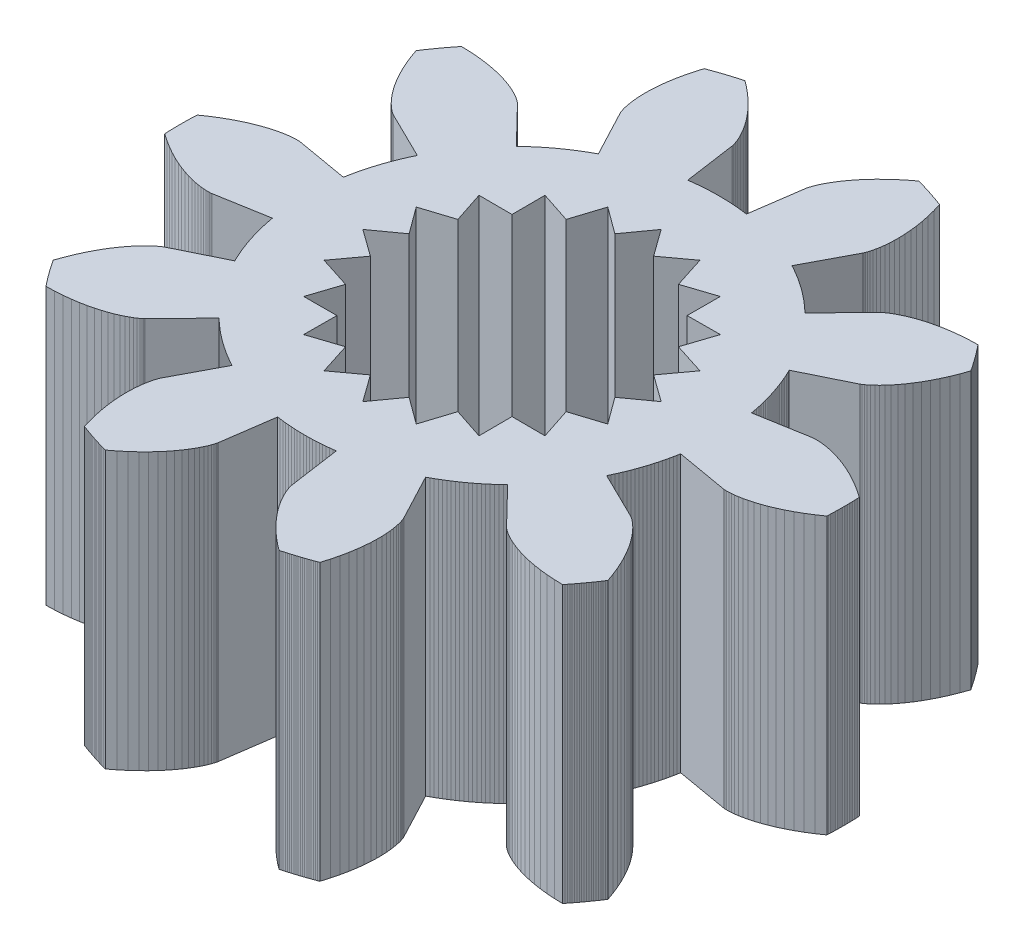
SolidWorks part; units mm, degrees
ref_plane "Front Plane" through (0, 0, 0) normal (0, 0, 1) x (1, 0, 0)
ref_plane "Top Plane" through (0, 0, 0) normal (0, 1, 0) x (1, 0, 0)
ref_plane "Right Plane" through (0, 0, 0) normal (1, 0, 0) x (0, 0, -1)
sketch "Sketch1" plane through (0, 0, 0) normal (0, 1, 0) x (1, 0, 0)
  line L0 (3.6947, -0.6418) -> (4.6291, -0.8041)
  line L1 (4.6291, -0.8041) -> (4.6332, -0.8047)
  line L2 (4.6332, -0.8047) -> (4.6455, -0.806)
  line L3 (4.6455, -0.806) -> (4.6659, -0.8073)
  line L4 (4.6659, -0.8073) -> (4.6947, -0.8081)
  line L5 (4.6947, -0.8081) -> (4.7316, -0.8074)
  line L6 (4.7316, -0.8074) -> (4.7767, -0.8048)
  line L7 (4.7767, -0.8048) -> (4.8297, -0.7994)
  line L8 (4.8297, -0.7994) -> (4.8907, -0.7907)
  line L9 (4.8907, -0.7907) -> (4.9593, -0.778)
  line L10 (4.9593, -0.778) -> (5.0353, -0.7605)
  line L11 (5.0353, -0.7605) -> (5.1184, -0.7378)
  line L12 (5.1184, -0.7378) -> (5.2084, -0.7091)
  line L13 (5.2084, -0.7091) -> (5.3047, -0.6738)
  line L14 (5.3047, -0.6738) -> (5.4071, -0.6314)
  line L15 (5.4071, -0.6314) -> (5.5151, -0.5813)
  line L16 (5.5151, -0.5813) -> (5.6282, -0.523)
  line L17 (5.6282, -0.523) -> (5.7459, -0.456)
  line L18 (5.7459, -0.456) -> (5.8676, -0.3797)
  line L19 (5.8676, -0.3797) -> (5.9928, -0.2937)
  line L20 (5.9928, -0.2937) -> (5.9942, -0.2628)
  line L21 (5.9942, -0.2628) -> (5.9955, -0.2319)
  line L22 (5.9955, -0.2319) -> (5.9966, -0.201)
  line L23 (5.9966, -0.201) -> (5.9976, -0.1701)
  line L24 (5.9976, -0.1701) -> (5.9984, -0.1392)
  line L25 (5.9984, -0.1392) -> (5.999, -0.1083)
  line L26 (5.999, -0.1083) -> (5.9995, -0.0773)
  line L27 (5.9995, -0.0773) -> (5.9998, -0.0464)
  line L28 (5.9998, -0.0464) -> (6, -0.0155)
  line L29 (6, -0.0155) -> (6, 0.0155)
  line L30 (6, 0.0155) -> (5.9998, 0.0464)
  line L31 (5.9998, 0.0464) -> (5.9995, 0.0773)
  line L32 (5.9995, 0.0773) -> (5.999, 0.1083)
  line L33 (5.999, 0.1083) -> (5.9984, 0.1392)
  line L34 (5.9984, 0.1392) -> (5.9976, 0.1701)
  line L35 (5.9976, 0.1701) -> (5.9966, 0.201)
  line L36 (5.9966, 0.201) -> (5.9955, 0.2319)
  line L37 (5.9955, 0.2319) -> (5.9942, 0.2628)
  line L38 (5.9942, 0.2628) -> (5.9928, 0.2937)
  line L39 (5.9928, 0.2937) -> (5.8676, 0.3797)
  line L40 (5.8676, 0.3797) -> (5.7459, 0.456)
  line L41 (5.7459, 0.456) -> (5.6282, 0.523)
  line L42 (5.6282, 0.523) -> (5.5151, 0.5813)
  line L43 (5.5151, 0.5813) -> (5.4071, 0.6314)
  line L44 (5.4071, 0.6314) -> (5.3047, 0.6738)
  line L45 (5.3047, 0.6738) -> (5.2084, 0.7091)
  line L46 (5.2084, 0.7091) -> (5.1184, 0.7378)
  line L47 (5.1184, 0.7378) -> (5.0353, 0.7605)
  line L48 (5.0353, 0.7605) -> (4.9593, 0.778)
  line L49 (4.9593, 0.778) -> (4.8907, 0.7907)
  line L50 (4.8907, 0.7907) -> (4.8297, 0.7994)
  line L51 (4.8297, 0.7994) -> (4.7767, 0.8048)
  line L52 (4.7767, 0.8048) -> (4.7316, 0.8074)
  line L53 (4.7316, 0.8074) -> (4.6947, 0.8081)
  line L54 (4.6947, 0.8081) -> (4.6659, 0.8073)
  line L55 (4.6659, 0.8073) -> (4.6455, 0.806)
  line L56 (4.6455, 0.806) -> (4.6332, 0.8047)
  line L57 (4.6332, 0.8047) -> (4.6291, 0.8041)
  line L58 (4.6291, 0.8041) -> (3.6947, 0.6418)
  line L59 (3.6947, 0.6418) -> (3.6847, 0.697)
  line L60 (3.6847, 0.697) -> (3.6738, 0.752)
  line L61 (3.6738, 0.752) -> (3.6621, 0.8069)
  line L62 (3.6621, 0.8069) -> (3.6497, 0.8617)
  line L63 (3.6497, 0.8617) -> (3.6364, 0.9162)
  line L64 (3.6364, 0.9162) -> (3.6222, 0.9705)
  line L65 (3.6222, 0.9705) -> (3.6073, 1.0246)
  line L66 (3.6073, 1.0246) -> (3.5916, 1.0785)
  line L67 (3.5916, 1.0785) -> (3.575, 1.1321)
  line L68 (3.575, 1.1321) -> (3.5577, 1.1855)
  line L69 (3.5577, 1.1855) -> (3.5396, 1.2386)
  line L70 (3.5396, 1.2386) -> (3.5206, 1.2914)
  line L71 (3.5206, 1.2914) -> (3.5009, 1.344)
  line L72 (3.5009, 1.344) -> (3.4804, 1.3962)
  line L73 (3.4804, 1.3962) -> (3.4591, 1.4481)
  line L74 (3.4591, 1.4481) -> (3.4371, 1.4997)
  line L75 (3.4371, 1.4997) -> (3.4142, 1.551)
  line L76 (3.4142, 1.551) -> (3.3906, 1.6019)
  line L77 (3.3906, 1.6019) -> (3.3663, 1.6525)
  line L78 (3.3663, 1.6525) -> (4.2177, 2.0704)
  line L79 (4.2177, 2.0704) -> (4.2213, 2.0723)
  line L80 (4.2213, 2.0723) -> (4.232, 2.0785)
  line L81 (4.232, 2.0785) -> (4.2494, 2.0894)
  line L82 (4.2494, 2.0894) -> (4.273, 2.1057)
  line L83 (4.273, 2.1057) -> (4.3025, 2.1279)
  line L84 (4.3025, 2.1279) -> (4.3374, 2.1566)
  line L85 (4.3374, 2.1566) -> (4.3773, 2.1921)
  line L86 (4.3773, 2.1921) -> (4.4214, 2.235)
  line L87 (4.4214, 2.235) -> (4.4694, 2.2856)
  line L88 (4.4694, 2.2856) -> (4.5207, 2.3444)
  line L89 (4.5207, 2.3444) -> (4.5746, 2.4117)
  line L90 (4.5746, 2.4117) -> (4.6304, 2.4877)
  line L91 (4.6304, 2.4877) -> (4.6877, 2.5729)
  line L92 (4.6877, 2.5729) -> (4.7456, 2.6674)
  line L93 (4.7456, 2.6674) -> (4.8035, 2.7714)
  line L94 (4.8035, 2.7714) -> (4.8607, 2.885)
  line L95 (4.8607, 2.885) -> (4.9165, 3.0085)
  line L96 (4.9165, 3.0085) -> (4.9702, 3.1417)
  line L97 (4.9702, 3.1417) -> (5.0209, 3.2848)
  line L98 (5.0209, 3.2848) -> (5.0039, 3.3107)
  line L99 (5.0039, 3.3107) -> (4.9868, 3.3364)
  line L100 (4.9868, 3.3364) -> (4.9695, 3.3621)
  line L101 (4.9695, 3.3621) -> (4.9521, 3.3877)
  line L102 (4.9521, 3.3877) -> (4.9346, 3.4132)
  line L103 (4.9346, 3.4132) -> (4.9169, 3.4386)
  line L104 (4.9169, 3.4386) -> (4.8992, 3.4639)
  line L105 (4.8992, 3.4639) -> (4.8812, 3.4891)
  line L106 (4.8812, 3.4891) -> (4.8632, 3.5142)
  line L107 (4.8632, 3.5142) -> (4.845, 3.5392)
  line L108 (4.845, 3.5392) -> (4.8267, 3.5641)
  line L109 (4.8267, 3.5641) -> (4.8082, 3.589)
  line L110 (4.8082, 3.589) -> (4.7897, 3.6137)
  line L111 (4.7897, 3.6137) -> (4.771, 3.6384)
  line L112 (4.771, 3.6384) -> (4.7522, 3.6629)
  line L113 (4.7522, 3.6629) -> (4.7332, 3.6874)
  line L114 (4.7332, 3.6874) -> (4.7141, 3.7117)
  line L115 (4.7141, 3.7117) -> (4.6949, 3.736)
  line L116 (4.6949, 3.736) -> (4.6756, 3.7601)
  line L117 (4.6756, 3.7601) -> (4.5238, 3.7561)
  line L118 (4.5238, 3.7561) -> (4.3805, 3.7462)
  line L119 (4.3805, 3.7462) -> (4.2459, 3.7313)
  line L120 (4.2459, 3.7313) -> (4.1201, 3.712)
  line L121 (4.1201, 3.712) -> (4.0033, 3.6891)
  line L122 (4.0033, 3.6891) -> (3.8956, 3.6632)
  line L123 (3.8956, 3.6632) -> (3.7969, 3.6351)
  line L124 (3.7969, 3.6351) -> (3.7072, 3.6054)
  line L125 (3.7072, 3.6054) -> (3.6266, 3.575)
  line L126 (3.6266, 3.575) -> (3.5549, 3.5444)
  line L127 (3.5549, 3.5444) -> (3.4919, 3.5144)
  line L128 (3.4919, 3.5144) -> (3.4374, 3.4856)
  line L129 (3.4374, 3.4856) -> (3.3914, 3.4587)
  line L130 (3.3914, 3.4587) -> (3.3533, 3.4344)
  line L131 (3.3533, 3.4344) -> (3.3231, 3.4132)
  line L132 (3.3231, 3.4132) -> (3.3003, 3.3957)
  line L133 (3.3003, 3.3957) -> (3.2845, 3.3826)
  line L134 (3.2845, 3.3826) -> (3.2754, 3.3743)
  line L135 (3.2754, 3.3743) -> (3.2724, 3.3715)
  line L136 (3.2724, 3.3715) -> (2.6118, 2.6909)
  line L137 (2.6118, 2.6909) -> (2.5713, 2.7297)
  line L138 (2.5713, 2.7297) -> (2.5301, 2.7678)
  line L139 (2.5301, 2.7678) -> (2.4884, 2.8054)
  line L140 (2.4884, 2.8054) -> (2.4462, 2.8423)
  line L141 (2.4462, 2.8423) -> (2.4034, 2.8786)
  line L142 (2.4034, 2.8786) -> (2.36, 2.9142)
  line L143 (2.36, 2.9142) -> (2.3161, 2.9492)
  line L144 (2.3161, 2.9492) -> (2.2717, 2.9836)
  line L145 (2.2717, 2.9836) -> (2.2268, 3.0172)
  line L146 (2.2268, 3.0172) -> (2.1814, 3.0502)
  line L147 (2.1814, 3.0502) -> (2.1355, 3.0825)
  line L148 (2.1355, 3.0825) -> (2.0892, 3.1141)
  line L149 (2.0892, 3.1141) -> (2.0423, 3.1451)
  line L150 (2.0423, 3.1451) -> (1.995, 3.1753)
  line L151 (1.995, 3.1753) -> (1.9473, 3.2048)
  line L152 (1.9473, 3.2048) -> (1.8991, 3.2336)
  line L153 (1.8991, 3.2336) -> (1.8505, 3.2616)
  line L154 (1.8505, 3.2616) -> (1.8015, 3.2889)
  line L155 (1.8015, 3.2889) -> (1.7521, 3.3155)
  line L156 (1.7521, 3.3155) -> (2.1952, 4.1541)
  line L157 (2.1952, 4.1541) -> (2.197, 4.1578)
  line L158 (2.197, 4.1578) -> (2.2021, 4.169)
  line L159 (2.2021, 4.169) -> (2.2097, 4.1881)
  line L160 (2.2097, 4.1881) -> (2.2192, 4.2152)
  line L161 (2.2192, 4.2152) -> (2.23, 4.2505)
  line L162 (2.23, 4.2505) -> (2.2415, 4.2942)
  line L163 (2.2415, 4.2942) -> (2.2528, 4.3463)
  line L164 (2.2528, 4.3463) -> (2.2633, 4.407)
  line L165 (2.2633, 4.407) -> (2.2724, 4.4762)
  line L166 (2.2724, 4.4762) -> (2.2793, 4.5538)
  line L167 (2.2793, 4.5538) -> (2.2834, 4.6399)
  line L168 (2.2834, 4.6399) -> (2.2838, 4.7343)
  line L169 (2.2838, 4.7343) -> (2.2801, 4.8369)
  line L170 (2.2801, 4.8369) -> (2.2714, 4.9474)
  line L171 (2.2714, 4.9474) -> (2.2571, 5.0655)
  line L172 (2.2571, 5.0655) -> (2.2366, 5.1911)
  line L173 (2.2366, 5.1911) -> (2.2092, 5.3237)
  line L174 (2.2092, 5.3237) -> (2.1743, 5.4631)
  line L175 (2.1743, 5.4631) -> (2.1312, 5.6087)
  line L176 (2.1312, 5.6087) -> (2.1023, 5.6196)
  line L177 (2.1023, 5.6196) -> (2.0733, 5.6304)
  line L178 (2.0733, 5.6304) -> (2.0442, 5.641)
  line L179 (2.0442, 5.641) -> (2.0151, 5.6515)
  line L180 (2.0151, 5.6515) -> (1.986, 5.6618)
  line L181 (1.986, 5.6618) -> (1.9568, 5.672)
  line L182 (1.9568, 5.672) -> (1.9275, 5.682)
  line L183 (1.9275, 5.682) -> (1.8982, 5.6918)
  line L184 (1.8982, 5.6918) -> (1.8688, 5.7015)
  line L185 (1.8688, 5.7015) -> (1.8394, 5.7111)
  line L186 (1.8394, 5.7111) -> (1.8099, 5.7205)
  line L187 (1.8099, 5.7205) -> (1.7804, 5.7298)
  line L188 (1.7804, 5.7298) -> (1.7508, 5.7389)
  line L189 (1.7508, 5.7389) -> (1.7212, 5.7478)
  line L190 (1.7212, 5.7478) -> (1.6916, 5.7566)
  line L191 (1.6916, 5.7566) -> (1.6619, 5.7653)
  line L192 (1.6619, 5.7653) -> (1.6321, 5.7737)
  line L193 (1.6321, 5.7737) -> (1.6023, 5.7821)
  line L194 (1.6023, 5.7821) -> (1.5725, 5.7903)
  line L195 (1.5725, 5.7903) -> (1.4521, 5.6977)
  line L196 (1.4521, 5.6977) -> (1.3419, 5.6055)
  line L197 (1.3419, 5.6055) -> (1.2418, 5.5143)
  line L198 (1.2418, 5.5143) -> (1.1514, 5.4248)
  line L199 (1.1514, 5.4248) -> (1.0704, 5.3376)
  line L200 (1.0704, 5.3376) -> (0.9984, 5.2533)
  line L201 (0.9984, 5.2533) -> (0.9351, 5.1726)
  line L202 (0.9351, 5.1726) -> (0.88, 5.0959)
  line L203 (0.88, 5.0959) -> (0.8327, 5.0239)
  line L204 (0.8327, 5.0239) -> (0.7926, 4.957)
  line L205 (0.7926, 4.957) -> (0.7593, 4.8957)
  line L206 (0.7593, 4.8957) -> (0.7322, 4.8404)
  line L207 (0.7322, 4.8404) -> (0.7107, 4.7916)
  line L208 (0.7107, 4.7916) -> (0.6942, 4.7495)
  line L209 (0.6942, 4.7495) -> (0.6822, 4.7146)
  line L210 (0.6822, 4.7146) -> (0.674, 4.687)
  line L211 (0.674, 4.687) -> (0.669, 4.6672)
  line L212 (0.669, 4.6672) -> (0.6665, 4.6551)
  line L213 (0.6665, 4.6551) -> (0.6658, 4.6511)
  line L214 (0.6658, 4.6511) -> (0.5314, 3.7122)
  line L215 (0.5314, 3.7122) -> (0.4757, 3.7197)
  line L216 (0.4757, 3.7197) -> (0.42, 3.7264)
  line L217 (0.42, 3.7264) -> (0.3642, 3.7323)
  line L218 (0.3642, 3.7323) -> (0.3083, 3.7373)
  line L219 (0.3083, 3.7373) -> (0.2524, 3.7415)
  line L220 (0.2524, 3.7415) -> (0.1963, 3.7449)
  line L221 (0.1963, 3.7449) -> (0.1403, 3.7474)
  line L222 (0.1403, 3.7474) -> (0.0842, 3.7491)
  line L223 (0.0842, 3.7491) -> (0.0281, 3.7499)
  line L224 (0.0281, 3.7499) -> (-0.0281, 3.7499)
  line L225 (-0.0281, 3.7499) -> (-0.0842, 3.7491)
  line L226 (-0.0842, 3.7491) -> (-0.1403, 3.7474)
  line L227 (-0.1403, 3.7474) -> (-0.1963, 3.7449)
  line L228 (-0.1963, 3.7449) -> (-0.2524, 3.7415)
  line L229 (-0.2524, 3.7415) -> (-0.3083, 3.7373)
  line L230 (-0.3083, 3.7373) -> (-0.3642, 3.7323)
  line L231 (-0.3642, 3.7323) -> (-0.42, 3.7264)
  line L232 (-0.42, 3.7264) -> (-0.4757, 3.7197)
  line L233 (-0.4757, 3.7197) -> (-0.5314, 3.7122)
  line L234 (-0.5314, 3.7122) -> (-0.6658, 4.6511)
  line L235 (-0.6658, 4.6511) -> (-0.6665, 4.6551)
  line L236 (-0.6665, 4.6551) -> (-0.669, 4.6672)
  line L237 (-0.669, 4.6672) -> (-0.674, 4.687)
  line L238 (-0.674, 4.687) -> (-0.6822, 4.7146)
  line L239 (-0.6822, 4.7146) -> (-0.6942, 4.7495)
  line L240 (-0.6942, 4.7495) -> (-0.7107, 4.7916)
  line L241 (-0.7107, 4.7916) -> (-0.7322, 4.8404)
  line L242 (-0.7322, 4.8404) -> (-0.7593, 4.8957)
  line L243 (-0.7593, 4.8957) -> (-0.7926, 4.957)
  line L244 (-0.7926, 4.957) -> (-0.8327, 5.0239)
  line L245 (-0.8327, 5.0239) -> (-0.88, 5.0959)
  line L246 (-0.88, 5.0959) -> (-0.9351, 5.1726)
  line L247 (-0.9351, 5.1726) -> (-0.9984, 5.2533)
  line L248 (-0.9984, 5.2533) -> (-1.0704, 5.3376)
  line L249 (-1.0704, 5.3376) -> (-1.1514, 5.4248)
  line L250 (-1.1514, 5.4248) -> (-1.2418, 5.5143)
  line L251 (-1.2418, 5.5143) -> (-1.3419, 5.6055)
  line L252 (-1.3419, 5.6055) -> (-1.4521, 5.6977)
  line L253 (-1.4521, 5.6977) -> (-1.5725, 5.7903)
  line L254 (-1.5725, 5.7903) -> (-1.6023, 5.7821)
  line L255 (-1.6023, 5.7821) -> (-1.6321, 5.7737)
  line L256 (-1.6321, 5.7737) -> (-1.6619, 5.7653)
  line L257 (-1.6619, 5.7653) -> (-1.6916, 5.7566)
  line L258 (-1.6916, 5.7566) -> (-1.7212, 5.7478)
  line L259 (-1.7212, 5.7478) -> (-1.7508, 5.7389)
  line L260 (-1.7508, 5.7389) -> (-1.7804, 5.7298)
  line L261 (-1.7804, 5.7298) -> (-1.8099, 5.7205)
  line L262 (-1.8099, 5.7205) -> (-1.8394, 5.7111)
  line L263 (-1.8394, 5.7111) -> (-1.8688, 5.7015)
  line L264 (-1.8688, 5.7015) -> (-1.8982, 5.6918)
  line L265 (-1.8982, 5.6918) -> (-1.9275, 5.682)
  line L266 (-1.9275, 5.682) -> (-1.9568, 5.672)
  line L267 (-1.9568, 5.672) -> (-1.986, 5.6618)
  line L268 (-1.986, 5.6618) -> (-2.0151, 5.6515)
  line L269 (-2.0151, 5.6515) -> (-2.0442, 5.641)
  line L270 (-2.0442, 5.641) -> (-2.0733, 5.6304)
  line L271 (-2.0733, 5.6304) -> (-2.1023, 5.6196)
  line L272 (-2.1023, 5.6196) -> (-2.1312, 5.6087)
  line L273 (-2.1312, 5.6087) -> (-2.1743, 5.4631)
  line L274 (-2.1743, 5.4631) -> (-2.2092, 5.3237)
  line L275 (-2.2092, 5.3237) -> (-2.2366, 5.1911)
  line L276 (-2.2366, 5.1911) -> (-2.2571, 5.0655)
  line L277 (-2.2571, 5.0655) -> (-2.2714, 4.9474)
  line L278 (-2.2714, 4.9474) -> (-2.2801, 4.8369)
  line L279 (-2.2801, 4.8369) -> (-2.2838, 4.7343)
  line L280 (-2.2838, 4.7343) -> (-2.2834, 4.6399)
  line L281 (-2.2834, 4.6399) -> (-2.2793, 4.5538)
  line L282 (-2.2793, 4.5538) -> (-2.2724, 4.4762)
  line L283 (-2.2724, 4.4762) -> (-2.2633, 4.407)
  line L284 (-2.2633, 4.407) -> (-2.2528, 4.3463)
  line L285 (-2.2528, 4.3463) -> (-2.2415, 4.2942)
  line L286 (-2.2415, 4.2942) -> (-2.23, 4.2505)
  line L287 (-2.23, 4.2505) -> (-2.2192, 4.2152)
  line L288 (-2.2192, 4.2152) -> (-2.2097, 4.1881)
  line L289 (-2.2097, 4.1881) -> (-2.2021, 4.169)
  line L290 (-2.2021, 4.169) -> (-2.197, 4.1578)
  line L291 (-2.197, 4.1578) -> (-2.1952, 4.1541)
  line L292 (-2.1952, 4.1541) -> (-1.7521, 3.3155)
  line L293 (-1.7521, 3.3155) -> (-1.8015, 3.2889)
  line L294 (-1.8015, 3.2889) -> (-1.8505, 3.2616)
  line L295 (-1.8505, 3.2616) -> (-1.8991, 3.2336)
  line L296 (-1.8991, 3.2336) -> (-1.9473, 3.2048)
  line L297 (-1.9473, 3.2048) -> (-1.995, 3.1753)
  line L298 (-1.995, 3.1753) -> (-2.0423, 3.1451)
  line L299 (-2.0423, 3.1451) -> (-2.0892, 3.1141)
  line L300 (-2.0892, 3.1141) -> (-2.1355, 3.0825)
  line L301 (-2.1355, 3.0825) -> (-2.1814, 3.0502)
  line L302 (-2.1814, 3.0502) -> (-2.2268, 3.0172)
  line L303 (-2.2268, 3.0172) -> (-2.2717, 2.9836)
  line L304 (-2.2717, 2.9836) -> (-2.3161, 2.9492)
  line L305 (-2.3161, 2.9492) -> (-2.36, 2.9142)
  line L306 (-2.36, 2.9142) -> (-2.4034, 2.8786)
  line L307 (-2.4034, 2.8786) -> (-2.4462, 2.8423)
  line L308 (-2.4462, 2.8423) -> (-2.4884, 2.8054)
  line L309 (-2.4884, 2.8054) -> (-2.5301, 2.7678)
  line L310 (-2.5301, 2.7678) -> (-2.5713, 2.7297)
  line L311 (-2.5713, 2.7297) -> (-2.6118, 2.6909)
  line L312 (-2.6118, 2.6909) -> (-3.2724, 3.3715)
  line L313 (-3.2724, 3.3715) -> (-3.2754, 3.3743)
  line L314 (-3.2754, 3.3743) -> (-3.2845, 3.3826)
  line L315 (-3.2845, 3.3826) -> (-3.3003, 3.3957)
  line L316 (-3.3003, 3.3957) -> (-3.3231, 3.4132)
  line L317 (-3.3231, 3.4132) -> (-3.3533, 3.4344)
  line L318 (-3.3533, 3.4344) -> (-3.3914, 3.4587)
  line L319 (-3.3914, 3.4587) -> (-3.4374, 3.4856)
  line L320 (-3.4374, 3.4856) -> (-3.4919, 3.5144)
  line L321 (-3.4919, 3.5144) -> (-3.5549, 3.5444)
  line L322 (-3.5549, 3.5444) -> (-3.6266, 3.575)
  line L323 (-3.6266, 3.575) -> (-3.7072, 3.6054)
  line L324 (-3.7072, 3.6054) -> (-3.7969, 3.6351)
  line L325 (-3.7969, 3.6351) -> (-3.8956, 3.6632)
  line L326 (-3.8956, 3.6632) -> (-4.0033, 3.6891)
  line L327 (-4.0033, 3.6891) -> (-4.1201, 3.712)
  line L328 (-4.1201, 3.712) -> (-4.2459, 3.7313)
  line L329 (-4.2459, 3.7313) -> (-4.3805, 3.7462)
  line L330 (-4.3805, 3.7462) -> (-4.5238, 3.7561)
  line L331 (-4.5238, 3.7561) -> (-4.6756, 3.7601)
  line L332 (-4.6756, 3.7601) -> (-4.6949, 3.736)
  line L333 (-4.6949, 3.736) -> (-4.7141, 3.7117)
  line L334 (-4.7141, 3.7117) -> (-4.7332, 3.6874)
  line L335 (-4.7332, 3.6874) -> (-4.7522, 3.6629)
  line L336 (-4.7522, 3.6629) -> (-4.771, 3.6384)
  line L337 (-4.771, 3.6384) -> (-4.7897, 3.6137)
  line L338 (-4.7897, 3.6137) -> (-4.8082, 3.589)
  line L339 (-4.8082, 3.589) -> (-4.8267, 3.5641)
  line L340 (-4.8267, 3.5641) -> (-4.845, 3.5392)
  line L341 (-4.845, 3.5392) -> (-4.8632, 3.5142)
  line L342 (-4.8632, 3.5142) -> (-4.8812, 3.4891)
  line L343 (-4.8812, 3.4891) -> (-4.8992, 3.4639)
  line L344 (-4.8992, 3.4639) -> (-4.9169, 3.4386)
  line L345 (-4.9169, 3.4386) -> (-4.9346, 3.4132)
  line L346 (-4.9346, 3.4132) -> (-4.9521, 3.3877)
  line L347 (-4.9521, 3.3877) -> (-4.9695, 3.3621)
  line L348 (-4.9695, 3.3621) -> (-4.9868, 3.3364)
  line L349 (-4.9868, 3.3364) -> (-5.0039, 3.3107)
  line L350 (-5.0039, 3.3107) -> (-5.0209, 3.2848)
  line L351 (-5.0209, 3.2848) -> (-4.9702, 3.1417)
  line L352 (-4.9702, 3.1417) -> (-4.9165, 3.0085)
  line L353 (-4.9165, 3.0085) -> (-4.8607, 2.885)
  line L354 (-4.8607, 2.885) -> (-4.8035, 2.7714)
  line L355 (-4.8035, 2.7714) -> (-4.7456, 2.6674)
  line L356 (-4.7456, 2.6674) -> (-4.6877, 2.5729)
  line L357 (-4.6877, 2.5729) -> (-4.6304, 2.4877)
  line L358 (-4.6304, 2.4877) -> (-4.5746, 2.4117)
  line L359 (-4.5746, 2.4117) -> (-4.5207, 2.3444)
  line L360 (-4.5207, 2.3444) -> (-4.4694, 2.2856)
  line L361 (-4.4694, 2.2856) -> (-4.4214, 2.235)
  line L362 (-4.4214, 2.235) -> (-4.3773, 2.1921)
  line L363 (-4.3773, 2.1921) -> (-4.3374, 2.1566)
  line L364 (-4.3374, 2.1566) -> (-4.3025, 2.1279)
  line L365 (-4.3025, 2.1279) -> (-4.273, 2.1057)
  line L366 (-4.273, 2.1057) -> (-4.2494, 2.0894)
  line L367 (-4.2494, 2.0894) -> (-4.232, 2.0785)
  line L368 (-4.232, 2.0785) -> (-4.2213, 2.0723)
  line L369 (-4.2213, 2.0723) -> (-4.2177, 2.0704)
  line L370 (-4.2177, 2.0704) -> (-3.3663, 1.6525)
  line L371 (-3.3663, 1.6525) -> (-3.3906, 1.6019)
  line L372 (-3.3906, 1.6019) -> (-3.4142, 1.551)
  line L373 (-3.4142, 1.551) -> (-3.4371, 1.4997)
  line L374 (-3.4371, 1.4997) -> (-3.4591, 1.4481)
  line L375 (-3.4591, 1.4481) -> (-3.4804, 1.3962)
  line L376 (-3.4804, 1.3962) -> (-3.5009, 1.344)
  line L377 (-3.5009, 1.344) -> (-3.5206, 1.2914)
  line L378 (-3.5206, 1.2914) -> (-3.5396, 1.2386)
  line L379 (-3.5396, 1.2386) -> (-3.5577, 1.1855)
  line L380 (-3.5577, 1.1855) -> (-3.575, 1.1321)
  line L381 (-3.575, 1.1321) -> (-3.5916, 1.0785)
  line L382 (-3.5916, 1.0785) -> (-3.6073, 1.0246)
  line L383 (-3.6073, 1.0246) -> (-3.6222, 0.9705)
  line L384 (-3.6222, 0.9705) -> (-3.6364, 0.9162)
  line L385 (-3.6364, 0.9162) -> (-3.6497, 0.8617)
  line L386 (-3.6497, 0.8617) -> (-3.6621, 0.8069)
  line L387 (-3.6621, 0.8069) -> (-3.6738, 0.752)
  line L388 (-3.6738, 0.752) -> (-3.6847, 0.697)
  line L389 (-3.6847, 0.697) -> (-3.6947, 0.6418)
  line L390 (-3.6947, 0.6418) -> (-4.6291, 0.8041)
  line L391 (-4.6291, 0.8041) -> (-4.6332, 0.8047)
  line L392 (-4.6332, 0.8047) -> (-4.6455, 0.806)
  line L393 (-4.6455, 0.806) -> (-4.6659, 0.8073)
  line L394 (-4.6659, 0.8073) -> (-4.6947, 0.8081)
  line L395 (-4.6947, 0.8081) -> (-4.7316, 0.8074)
  line L396 (-4.7316, 0.8074) -> (-4.7767, 0.8048)
  line L397 (-4.7767, 0.8048) -> (-4.8297, 0.7994)
  line L398 (-4.8297, 0.7994) -> (-4.8907, 0.7907)
  line L399 (-4.8907, 0.7907) -> (-4.9593, 0.778)
  line L400 (-4.9593, 0.778) -> (-5.0353, 0.7605)
  line L401 (-5.0353, 0.7605) -> (-5.1184, 0.7378)
  line L402 (-5.1184, 0.7378) -> (-5.2084, 0.7091)
  line L403 (-5.2084, 0.7091) -> (-5.3047, 0.6738)
  line L404 (-5.3047, 0.6738) -> (-5.4071, 0.6314)
  line L405 (-5.4071, 0.6314) -> (-5.5151, 0.5813)
  line L406 (-5.5151, 0.5813) -> (-5.6282, 0.523)
  line L407 (-5.6282, 0.523) -> (-5.7459, 0.456)
  line L408 (-5.7459, 0.456) -> (-5.8676, 0.3797)
  line L409 (-5.8676, 0.3797) -> (-5.9928, 0.2937)
  line L410 (-5.9928, 0.2937) -> (-5.9942, 0.2628)
  line L411 (-5.9942, 0.2628) -> (-5.9955, 0.2319)
  line L412 (-5.9955, 0.2319) -> (-5.9966, 0.201)
  line L413 (-5.9966, 0.201) -> (-5.9976, 0.1701)
  line L414 (-5.9976, 0.1701) -> (-5.9984, 0.1392)
  line L415 (-5.9984, 0.1392) -> (-5.999, 0.1083)
  line L416 (-5.999, 0.1083) -> (-5.9995, 0.0773)
  line L417 (-5.9995, 0.0773) -> (-5.9998, 0.0464)
  line L418 (-5.9998, 0.0464) -> (-6, 0.0155)
  line L419 (-6, 0.0155) -> (-6, -0.0155)
  line L420 (-6, -0.0155) -> (-5.9998, -0.0464)
  line L421 (-5.9998, -0.0464) -> (-5.9995, -0.0773)
  line L422 (-5.9995, -0.0773) -> (-5.999, -0.1083)
  line L423 (-5.999, -0.1083) -> (-5.9984, -0.1392)
  line L424 (-5.9984, -0.1392) -> (-5.9976, -0.1701)
  line L425 (-5.9976, -0.1701) -> (-5.9966, -0.201)
  line L426 (-5.9966, -0.201) -> (-5.9955, -0.2319)
  line L427 (-5.9955, -0.2319) -> (-5.9942, -0.2628)
  line L428 (-5.9942, -0.2628) -> (-5.9928, -0.2937)
  line L429 (-5.9928, -0.2937) -> (-5.8676, -0.3797)
  line L430 (-5.8676, -0.3797) -> (-5.7459, -0.456)
  line L431 (-5.7459, -0.456) -> (-5.6282, -0.523)
  line L432 (-5.6282, -0.523) -> (-5.5151, -0.5813)
  line L433 (-5.5151, -0.5813) -> (-5.4071, -0.6314)
  line L434 (-5.4071, -0.6314) -> (-5.3047, -0.6738)
  line L435 (-5.3047, -0.6738) -> (-5.2084, -0.7091)
  line L436 (-5.2084, -0.7091) -> (-5.1184, -0.7378)
  line L437 (-5.1184, -0.7378) -> (-5.0353, -0.7605)
  line L438 (-5.0353, -0.7605) -> (-4.9593, -0.778)
  line L439 (-4.9593, -0.778) -> (-4.8907, -0.7907)
  line L440 (-4.8907, -0.7907) -> (-4.8297, -0.7994)
  line L441 (-4.8297, -0.7994) -> (-4.7767, -0.8048)
  line L442 (-4.7767, -0.8048) -> (-4.7316, -0.8074)
  line L443 (-4.7316, -0.8074) -> (-4.6947, -0.8081)
  line L444 (-4.6947, -0.8081) -> (-4.6659, -0.8073)
  line L445 (-4.6659, -0.8073) -> (-4.6455, -0.806)
  line L446 (-4.6455, -0.806) -> (-4.6332, -0.8047)
  line L447 (-4.6332, -0.8047) -> (-4.6291, -0.8041)
  line L448 (-4.6291, -0.8041) -> (-3.6947, -0.6418)
  line L449 (-3.6947, -0.6418) -> (-3.6847, -0.697)
  line L450 (-3.6847, -0.697) -> (-3.6738, -0.752)
  line L451 (-3.6738, -0.752) -> (-3.6621, -0.8069)
  line L452 (-3.6621, -0.8069) -> (-3.6497, -0.8617)
  line L453 (-3.6497, -0.8617) -> (-3.6364, -0.9162)
  line L454 (-3.6364, -0.9162) -> (-3.6222, -0.9705)
  line L455 (-3.6222, -0.9705) -> (-3.6073, -1.0246)
  line L456 (-3.6073, -1.0246) -> (-3.5916, -1.0785)
  line L457 (-3.5916, -1.0785) -> (-3.575, -1.1321)
  line L458 (-3.575, -1.1321) -> (-3.5577, -1.1855)
  line L459 (-3.5577, -1.1855) -> (-3.5396, -1.2386)
  line L460 (-3.5396, -1.2386) -> (-3.5206, -1.2914)
  line L461 (-3.5206, -1.2914) -> (-3.5009, -1.344)
  line L462 (-3.5009, -1.344) -> (-3.4804, -1.3962)
  line L463 (-3.4804, -1.3962) -> (-3.4591, -1.4481)
  line L464 (-3.4591, -1.4481) -> (-3.4371, -1.4997)
  line L465 (-3.4371, -1.4997) -> (-3.4142, -1.551)
  line L466 (-3.4142, -1.551) -> (-3.3906, -1.6019)
  line L467 (-3.3906, -1.6019) -> (-3.3663, -1.6525)
  line L468 (-3.3663, -1.6525) -> (-4.2177, -2.0704)
  line L469 (-4.2177, -2.0704) -> (-4.2213, -2.0723)
  line L470 (-4.2213, -2.0723) -> (-4.232, -2.0785)
  line L471 (-4.232, -2.0785) -> (-4.2494, -2.0894)
  line L472 (-4.2494, -2.0894) -> (-4.273, -2.1057)
  line L473 (-4.273, -2.1057) -> (-4.3025, -2.1279)
  line L474 (-4.3025, -2.1279) -> (-4.3374, -2.1566)
  line L475 (-4.3374, -2.1566) -> (-4.3773, -2.1921)
  line L476 (-4.3773, -2.1921) -> (-4.4214, -2.235)
  line L477 (-4.4214, -2.235) -> (-4.4694, -2.2856)
  line L478 (-4.4694, -2.2856) -> (-4.5207, -2.3444)
  line L479 (-4.5207, -2.3444) -> (-4.5746, -2.4117)
  line L480 (-4.5746, -2.4117) -> (-4.6304, -2.4877)
  line L481 (-4.6304, -2.4877) -> (-4.6877, -2.5729)
  line L482 (-4.6877, -2.5729) -> (-4.7456, -2.6674)
  line L483 (-4.7456, -2.6674) -> (-4.8035, -2.7714)
  line L484 (-4.8035, -2.7714) -> (-4.8607, -2.885)
  line L485 (-4.8607, -2.885) -> (-4.9165, -3.0085)
  line L486 (-4.9165, -3.0085) -> (-4.9702, -3.1417)
  line L487 (-4.9702, -3.1417) -> (-5.0209, -3.2848)
  line L488 (-5.0209, -3.2848) -> (-5.0039, -3.3107)
  line L489 (-5.0039, -3.3107) -> (-4.9868, -3.3364)
  line L490 (-4.9868, -3.3364) -> (-4.9695, -3.3621)
  line L491 (-4.9695, -3.3621) -> (-4.9521, -3.3877)
  line L492 (-4.9521, -3.3877) -> (-4.9346, -3.4132)
  line L493 (-4.9346, -3.4132) -> (-4.9169, -3.4386)
  line L494 (-4.9169, -3.4386) -> (-4.8992, -3.4639)
  line L495 (-4.8992, -3.4639) -> (-4.8812, -3.4891)
  line L496 (-4.8812, -3.4891) -> (-4.8632, -3.5142)
  line L497 (-4.8632, -3.5142) -> (-4.845, -3.5392)
  line L498 (-4.845, -3.5392) -> (-4.8267, -3.5641)
  line L499 (-4.8267, -3.5641) -> (-4.8082, -3.589)
  line L500 (-4.8082, -3.589) -> (-4.7897, -3.6137)
  line L501 (-4.7897, -3.6137) -> (-4.771, -3.6384)
  line L502 (-4.771, -3.6384) -> (-4.7522, -3.6629)
  line L503 (-4.7522, -3.6629) -> (-4.7332, -3.6874)
  line L504 (-4.7332, -3.6874) -> (-4.7141, -3.7117)
  line L505 (-4.7141, -3.7117) -> (-4.6949, -3.736)
  line L506 (-4.6949, -3.736) -> (-4.6756, -3.7601)
  line L507 (-4.6756, -3.7601) -> (-4.5238, -3.7561)
  line L508 (-4.5238, -3.7561) -> (-4.3805, -3.7462)
  line L509 (-4.3805, -3.7462) -> (-4.2459, -3.7313)
  line L510 (-4.2459, -3.7313) -> (-4.1201, -3.712)
  line L511 (-4.1201, -3.712) -> (-4.0033, -3.6891)
  line L512 (-4.0033, -3.6891) -> (-3.8956, -3.6632)
  line L513 (-3.8956, -3.6632) -> (-3.7969, -3.6351)
  line L514 (-3.7969, -3.6351) -> (-3.7072, -3.6054)
  line L515 (-3.7072, -3.6054) -> (-3.6266, -3.575)
  line L516 (-3.6266, -3.575) -> (-3.5549, -3.5444)
  line L517 (-3.5549, -3.5444) -> (-3.4919, -3.5144)
  line L518 (-3.4919, -3.5144) -> (-3.4374, -3.4856)
  line L519 (-3.4374, -3.4856) -> (-3.3914, -3.4587)
  line L520 (-3.3914, -3.4587) -> (-3.3533, -3.4344)
  line L521 (-3.3533, -3.4344) -> (-3.3231, -3.4132)
  line L522 (-3.3231, -3.4132) -> (-3.3003, -3.3957)
  line L523 (-3.3003, -3.3957) -> (-3.2845, -3.3826)
  line L524 (-3.2845, -3.3826) -> (-3.2754, -3.3743)
  line L525 (-3.2754, -3.3743) -> (-3.2724, -3.3715)
  line L526 (-3.2724, -3.3715) -> (-2.6118, -2.6909)
  line L527 (-2.6118, -2.6909) -> (-2.5713, -2.7297)
  line L528 (-2.5713, -2.7297) -> (-2.5301, -2.7678)
  line L529 (-2.5301, -2.7678) -> (-2.4884, -2.8054)
  line L530 (-2.4884, -2.8054) -> (-2.4462, -2.8423)
  line L531 (-2.4462, -2.8423) -> (-2.4034, -2.8786)
  line L532 (-2.4034, -2.8786) -> (-2.36, -2.9142)
  line L533 (-2.36, -2.9142) -> (-2.3161, -2.9492)
  line L534 (-2.3161, -2.9492) -> (-2.2717, -2.9836)
  line L535 (-2.2717, -2.9836) -> (-2.2268, -3.0172)
  line L536 (-2.2268, -3.0172) -> (-2.1814, -3.0502)
  line L537 (-2.1814, -3.0502) -> (-2.1355, -3.0825)
  line L538 (-2.1355, -3.0825) -> (-2.0892, -3.1141)
  line L539 (-2.0892, -3.1141) -> (-2.0423, -3.1451)
  line L540 (-2.0423, -3.1451) -> (-1.995, -3.1753)
  line L541 (-1.995, -3.1753) -> (-1.9473, -3.2048)
  line L542 (-1.9473, -3.2048) -> (-1.8991, -3.2336)
  line L543 (-1.8991, -3.2336) -> (-1.8505, -3.2616)
  line L544 (-1.8505, -3.2616) -> (-1.8015, -3.2889)
  line L545 (-1.8015, -3.2889) -> (-1.7521, -3.3155)
  line L546 (-1.7521, -3.3155) -> (-2.1952, -4.1541)
  line L547 (-2.1952, -4.1541) -> (-2.197, -4.1578)
  line L548 (-2.197, -4.1578) -> (-2.2021, -4.169)
  line L549 (-2.2021, -4.169) -> (-2.2097, -4.1881)
  line L550 (-2.2097, -4.1881) -> (-2.2192, -4.2152)
  line L551 (-2.2192, -4.2152) -> (-2.23, -4.2505)
  line L552 (-2.23, -4.2505) -> (-2.2415, -4.2942)
  line L553 (-2.2415, -4.2942) -> (-2.2528, -4.3463)
  line L554 (-2.2528, -4.3463) -> (-2.2633, -4.407)
  line L555 (-2.2633, -4.407) -> (-2.2724, -4.4762)
  line L556 (-2.2724, -4.4762) -> (-2.2793, -4.5538)
  line L557 (-2.2793, -4.5538) -> (-2.2834, -4.6399)
  line L558 (-2.2834, -4.6399) -> (-2.2838, -4.7343)
  line L559 (-2.2838, -4.7343) -> (-2.2801, -4.8369)
  line L560 (-2.2801, -4.8369) -> (-2.2714, -4.9474)
  line L561 (-2.2714, -4.9474) -> (-2.2571, -5.0655)
  line L562 (-2.2571, -5.0655) -> (-2.2366, -5.1911)
  line L563 (-2.2366, -5.1911) -> (-2.2092, -5.3237)
  line L564 (-2.2092, -5.3237) -> (-2.1743, -5.4631)
  line L565 (-2.1743, -5.4631) -> (-2.1312, -5.6087)
  line L566 (-2.1312, -5.6087) -> (-2.1023, -5.6196)
  line L567 (-2.1023, -5.6196) -> (-2.0733, -5.6304)
  line L568 (-2.0733, -5.6304) -> (-2.0442, -5.641)
  line L569 (-2.0442, -5.641) -> (-2.0151, -5.6515)
  line L570 (-2.0151, -5.6515) -> (-1.986, -5.6618)
  line L571 (-1.986, -5.6618) -> (-1.9568, -5.672)
  line L572 (-1.9568, -5.672) -> (-1.9275, -5.682)
  line L573 (-1.9275, -5.682) -> (-1.8982, -5.6918)
  line L574 (-1.8982, -5.6918) -> (-1.8688, -5.7015)
  line L575 (-1.8688, -5.7015) -> (-1.8394, -5.7111)
  line L576 (-1.8394, -5.7111) -> (-1.8099, -5.7205)
  line L577 (-1.8099, -5.7205) -> (-1.7804, -5.7298)
  line L578 (-1.7804, -5.7298) -> (-1.7508, -5.7389)
  line L579 (-1.7508, -5.7389) -> (-1.7212, -5.7478)
  line L580 (-1.7212, -5.7478) -> (-1.6916, -5.7566)
  line L581 (-1.6916, -5.7566) -> (-1.6619, -5.7653)
  line L582 (-1.6619, -5.7653) -> (-1.6321, -5.7737)
  line L583 (-1.6321, -5.7737) -> (-1.6023, -5.7821)
  line L584 (-1.6023, -5.7821) -> (-1.5725, -5.7903)
  line L585 (-1.5725, -5.7903) -> (-1.4521, -5.6977)
  line L586 (-1.4521, -5.6977) -> (-1.3419, -5.6055)
  line L587 (-1.3419, -5.6055) -> (-1.2418, -5.5143)
  line L588 (-1.2418, -5.5143) -> (-1.1514, -5.4248)
  line L589 (-1.1514, -5.4248) -> (-1.0704, -5.3376)
  line L590 (-1.0704, -5.3376) -> (-0.9984, -5.2533)
  line L591 (-0.9984, -5.2533) -> (-0.9351, -5.1726)
  line L592 (-0.9351, -5.1726) -> (-0.88, -5.0959)
  line L593 (-0.88, -5.0959) -> (-0.8327, -5.0239)
  line L594 (-0.8327, -5.0239) -> (-0.7926, -4.957)
  line L595 (-0.7926, -4.957) -> (-0.7593, -4.8957)
  line L596 (-0.7593, -4.8957) -> (-0.7322, -4.8404)
  line L597 (-0.7322, -4.8404) -> (-0.7107, -4.7916)
  line L598 (-0.7107, -4.7916) -> (-0.6942, -4.7495)
  line L599 (-0.6942, -4.7495) -> (-0.6822, -4.7146)
  line L600 (-0.6822, -4.7146) -> (-0.674, -4.687)
  line L601 (-0.674, -4.687) -> (-0.669, -4.6672)
  line L602 (-0.669, -4.6672) -> (-0.6665, -4.6551)
  line L603 (-0.6665, -4.6551) -> (-0.6658, -4.6511)
  line L604 (-0.6658, -4.6511) -> (-0.5314, -3.7122)
  line L605 (-0.5314, -3.7122) -> (-0.4757, -3.7197)
  line L606 (-0.4757, -3.7197) -> (-0.42, -3.7264)
  line L607 (-0.42, -3.7264) -> (-0.3642, -3.7323)
  line L608 (-0.3642, -3.7323) -> (-0.3083, -3.7373)
  line L609 (-0.3083, -3.7373) -> (-0.2524, -3.7415)
  line L610 (-0.2524, -3.7415) -> (-0.1963, -3.7449)
  line L611 (-0.1963, -3.7449) -> (-0.1403, -3.7474)
  line L612 (-0.1403, -3.7474) -> (-0.0842, -3.7491)
  line L613 (-0.0842, -3.7491) -> (-0.0281, -3.7499)
  line L614 (-0.0281, -3.7499) -> (0.0281, -3.7499)
  line L615 (0.0281, -3.7499) -> (0.0842, -3.7491)
  line L616 (0.0842, -3.7491) -> (0.1403, -3.7474)
  line L617 (0.1403, -3.7474) -> (0.1963, -3.7449)
  line L618 (0.1963, -3.7449) -> (0.2524, -3.7415)
  line L619 (0.2524, -3.7415) -> (0.3083, -3.7373)
  line L620 (0.3083, -3.7373) -> (0.3642, -3.7323)
  line L621 (0.3642, -3.7323) -> (0.42, -3.7264)
  line L622 (0.42, -3.7264) -> (0.4757, -3.7197)
  line L623 (0.4757, -3.7197) -> (0.5314, -3.7122)
  line L624 (0.5314, -3.7122) -> (0.6658, -4.6511)
  line L625 (0.6658, -4.6511) -> (0.6665, -4.6551)
  line L626 (0.6665, -4.6551) -> (0.669, -4.6672)
  line L627 (0.669, -4.6672) -> (0.674, -4.687)
  line L628 (0.674, -4.687) -> (0.6822, -4.7146)
  line L629 (0.6822, -4.7146) -> (0.6942, -4.7495)
  line L630 (0.6942, -4.7495) -> (0.7107, -4.7916)
  line L631 (0.7107, -4.7916) -> (0.7322, -4.8404)
  line L632 (0.7322, -4.8404) -> (0.7593, -4.8957)
  line L633 (0.7593, -4.8957) -> (0.7926, -4.957)
  line L634 (0.7926, -4.957) -> (0.8327, -5.0239)
  line L635 (0.8327, -5.0239) -> (0.88, -5.0959)
  line L636 (0.88, -5.0959) -> (0.9351, -5.1726)
  line L637 (0.9351, -5.1726) -> (0.9984, -5.2533)
  line L638 (0.9984, -5.2533) -> (1.0704, -5.3376)
  line L639 (1.0704, -5.3376) -> (1.1514, -5.4248)
  line L640 (1.1514, -5.4248) -> (1.2418, -5.5143)
  line L641 (1.2418, -5.5143) -> (1.3419, -5.6055)
  line L642 (1.3419, -5.6055) -> (1.4521, -5.6977)
  line L643 (1.4521, -5.6977) -> (1.5725, -5.7903)
  line L644 (1.5725, -5.7903) -> (1.6023, -5.7821)
  line L645 (1.6023, -5.7821) -> (1.6321, -5.7737)
  line L646 (1.6321, -5.7737) -> (1.6619, -5.7653)
  line L647 (1.6619, -5.7653) -> (1.6916, -5.7566)
  line L648 (1.6916, -5.7566) -> (1.7212, -5.7478)
  line L649 (1.7212, -5.7478) -> (1.7508, -5.7389)
  line L650 (1.7508, -5.7389) -> (1.7804, -5.7298)
  line L651 (1.7804, -5.7298) -> (1.8099, -5.7205)
  line L652 (1.8099, -5.7205) -> (1.8394, -5.7111)
  line L653 (1.8394, -5.7111) -> (1.8688, -5.7015)
  line L654 (1.8688, -5.7015) -> (1.8982, -5.6918)
  line L655 (1.8982, -5.6918) -> (1.9275, -5.682)
  line L656 (1.9275, -5.682) -> (1.9568, -5.672)
  line L657 (1.9568, -5.672) -> (1.986, -5.6618)
  line L658 (1.986, -5.6618) -> (2.0151, -5.6515)
  line L659 (2.0151, -5.6515) -> (2.0442, -5.641)
  line L660 (2.0442, -5.641) -> (2.0733, -5.6304)
  line L661 (2.0733, -5.6304) -> (2.1023, -5.6196)
  line L662 (2.1023, -5.6196) -> (2.1312, -5.6087)
  line L663 (2.1312, -5.6087) -> (2.1743, -5.4631)
  line L664 (2.1743, -5.4631) -> (2.2092, -5.3237)
  line L665 (2.2092, -5.3237) -> (2.2366, -5.1911)
  line L666 (2.2366, -5.1911) -> (2.2571, -5.0655)
  line L667 (2.2571, -5.0655) -> (2.2714, -4.9474)
  line L668 (2.2714, -4.9474) -> (2.2801, -4.8369)
  line L669 (2.2801, -4.8369) -> (2.2838, -4.7343)
  line L670 (2.2838, -4.7343) -> (2.2834, -4.6399)
  line L671 (2.2834, -4.6399) -> (2.2793, -4.5538)
  line L672 (2.2793, -4.5538) -> (2.2724, -4.4762)
  line L673 (2.2724, -4.4762) -> (2.2633, -4.407)
  line L674 (2.2633, -4.407) -> (2.2528, -4.3463)
  line L675 (2.2528, -4.3463) -> (2.2415, -4.2942)
  line L676 (2.2415, -4.2942) -> (2.23, -4.2505)
  line L677 (2.23, -4.2505) -> (2.2192, -4.2152)
  line L678 (2.2192, -4.2152) -> (2.2097, -4.1881)
  line L679 (2.2097, -4.1881) -> (2.2021, -4.169)
  line L680 (2.2021, -4.169) -> (2.197, -4.1578)
  line L681 (2.197, -4.1578) -> (2.1952, -4.1541)
  line L682 (2.1952, -4.1541) -> (1.7521, -3.3155)
  line L683 (1.7521, -3.3155) -> (1.8015, -3.2889)
  line L684 (1.8015, -3.2889) -> (1.8505, -3.2616)
  line L685 (1.8505, -3.2616) -> (1.8991, -3.2336)
  line L686 (1.8991, -3.2336) -> (1.9473, -3.2048)
  line L687 (1.9473, -3.2048) -> (1.995, -3.1753)
  line L688 (1.995, -3.1753) -> (2.0423, -3.1451)
  line L689 (2.0423, -3.1451) -> (2.0892, -3.1141)
  line L690 (2.0892, -3.1141) -> (2.1355, -3.0825)
  line L691 (2.1355, -3.0825) -> (2.1814, -3.0502)
  line L692 (2.1814, -3.0502) -> (2.2268, -3.0172)
  line L693 (2.2268, -3.0172) -> (2.2717, -2.9836)
  line L694 (2.2717, -2.9836) -> (2.3161, -2.9492)
  line L695 (2.3161, -2.9492) -> (2.36, -2.9142)
  line L696 (2.36, -2.9142) -> (2.4034, -2.8786)
  line L697 (2.4034, -2.8786) -> (2.4462, -2.8423)
  line L698 (2.4462, -2.8423) -> (2.4884, -2.8054)
  line L699 (2.4884, -2.8054) -> (2.5301, -2.7678)
  line L700 (2.5301, -2.7678) -> (2.5713, -2.7297)
  line L701 (2.5713, -2.7297) -> (2.6118, -2.6909)
  line L702 (2.6118, -2.6909) -> (3.2724, -3.3715)
  line L703 (3.2724, -3.3715) -> (3.2754, -3.3743)
  line L704 (3.2754, -3.3743) -> (3.2845, -3.3826)
  line L705 (3.2845, -3.3826) -> (3.3003, -3.3957)
  line L706 (3.3003, -3.3957) -> (3.3231, -3.4132)
  line L707 (3.3231, -3.4132) -> (3.3533, -3.4344)
  line L708 (3.3533, -3.4344) -> (3.3914, -3.4587)
  line L709 (3.3914, -3.4587) -> (3.4374, -3.4856)
  line L710 (3.4374, -3.4856) -> (3.4919, -3.5144)
  line L711 (3.4919, -3.5144) -> (3.5549, -3.5444)
  line L712 (3.5549, -3.5444) -> (3.6266, -3.575)
  line L713 (3.6266, -3.575) -> (3.7072, -3.6054)
  line L714 (3.7072, -3.6054) -> (3.7969, -3.6351)
  line L715 (3.7969, -3.6351) -> (3.8956, -3.6632)
  line L716 (3.8956, -3.6632) -> (4.0033, -3.6891)
  line L717 (4.0033, -3.6891) -> (4.1201, -3.712)
  line L718 (4.1201, -3.712) -> (4.2459, -3.7313)
  line L719 (4.2459, -3.7313) -> (4.3805, -3.7462)
  line L720 (4.3805, -3.7462) -> (4.5238, -3.7561)
  line L721 (4.5238, -3.7561) -> (4.6756, -3.7601)
  line L722 (4.6756, -3.7601) -> (4.6949, -3.736)
  line L723 (4.6949, -3.736) -> (4.7141, -3.7117)
  line L724 (4.7141, -3.7117) -> (4.7332, -3.6874)
  line L725 (4.7332, -3.6874) -> (4.7522, -3.6629)
  line L726 (4.7522, -3.6629) -> (4.771, -3.6384)
  line L727 (4.771, -3.6384) -> (4.7897, -3.6137)
  line L728 (4.7897, -3.6137) -> (4.8082, -3.589)
  line L729 (4.8082, -3.589) -> (4.8267, -3.5641)
  line L730 (4.8267, -3.5641) -> (4.845, -3.5392)
  line L731 (4.845, -3.5392) -> (4.8632, -3.5142)
  line L732 (4.8632, -3.5142) -> (4.8812, -3.4891)
  line L733 (4.8812, -3.4891) -> (4.8992, -3.4639)
  line L734 (4.8992, -3.4639) -> (4.9169, -3.4386)
  line L735 (4.9169, -3.4386) -> (4.9346, -3.4132)
  line L736 (4.9346, -3.4132) -> (4.9521, -3.3877)
  line L737 (4.9521, -3.3877) -> (4.9695, -3.3621)
  line L738 (4.9695, -3.3621) -> (4.9868, -3.3364)
  line L739 (4.9868, -3.3364) -> (5.0039, -3.3107)
  line L740 (5.0039, -3.3107) -> (5.0209, -3.2848)
  line L741 (5.0209, -3.2848) -> (4.9702, -3.1417)
  line L742 (4.9702, -3.1417) -> (4.9165, -3.0085)
  line L743 (4.9165, -3.0085) -> (4.8607, -2.885)
  line L744 (4.8607, -2.885) -> (4.8035, -2.7714)
  line L745 (4.8035, -2.7714) -> (4.7456, -2.6674)
  line L746 (4.7456, -2.6674) -> (4.6877, -2.5729)
  line L747 (4.6877, -2.5729) -> (4.6304, -2.4877)
  line L748 (4.6304, -2.4877) -> (4.5746, -2.4117)
  line L749 (4.5746, -2.4117) -> (4.5207, -2.3444)
  line L750 (4.5207, -2.3444) -> (4.4694, -2.2856)
  line L751 (4.4694, -2.2856) -> (4.4214, -2.235)
  line L752 (4.4214, -2.235) -> (4.3773, -2.1921)
  line L753 (4.3773, -2.1921) -> (4.3374, -2.1566)
  line L754 (4.3374, -2.1566) -> (4.3025, -2.1279)
  line L755 (4.3025, -2.1279) -> (4.273, -2.1057)
  line L756 (4.273, -2.1057) -> (4.2494, -2.0894)
  line L757 (4.2494, -2.0894) -> (4.232, -2.0785)
  line L758 (4.232, -2.0785) -> (4.2213, -2.0723)
  line L759 (4.2213, -2.0723) -> (4.2177, -2.0704)
  line L760 (4.2177, -2.0704) -> (3.3663, -1.6525)
  line L761 (3.3663, -1.6525) -> (3.3906, -1.6019)
  line L762 (3.3906, -1.6019) -> (3.4142, -1.551)
  line L763 (3.4142, -1.551) -> (3.4371, -1.4997)
  line L764 (3.4371, -1.4997) -> (3.4591, -1.4481)
  line L765 (3.4591, -1.4481) -> (3.4804, -1.3962)
  line L766 (3.4804, -1.3962) -> (3.5009, -1.344)
  line L767 (3.5009, -1.344) -> (3.5206, -1.2914)
  line L768 (3.5206, -1.2914) -> (3.5396, -1.2386)
  line L769 (3.5396, -1.2386) -> (3.5577, -1.1855)
  line L770 (3.5577, -1.1855) -> (3.575, -1.1321)
  line L771 (3.575, -1.1321) -> (3.5916, -1.0785)
  line L772 (3.5916, -1.0785) -> (3.6073, -1.0246)
  line L773 (3.6073, -1.0246) -> (3.6222, -0.9705)
  line L774 (3.6222, -0.9705) -> (3.6364, -0.9162)
  line L775 (3.6364, -0.9162) -> (3.6497, -0.8617)
  line L776 (3.6497, -0.8617) -> (3.6621, -0.8069)
  line L777 (3.6621, -0.8069) -> (3.6738, -0.752)
  line L778 (3.6738, -0.752) -> (3.6847, -0.697)
  line L779 (3.6847, -0.697) -> (3.6947, -0.6418)
extrude "Boss-Extrude1" add sketch "Sketch1" along normal blind 5
sketch "Sketch2" plane through (0, 5, 0) normal (0, 1, 0) x (1, 0, 0)
  circle A0 centre (0, 0) radius 1.5
  dimension "D1" = 3
extrude "Cut-Extrude1" cut sketch "Sketch2" against normal through all
sketch "Sketch3" plane through (0, 5, 0) normal (0, 1, 0) x (1, 0, 0)
  circle A0 centre (0, 0) radius 5
  dimension "D1" = 10
sketch "Sketch4" plane through (0, 5, 0) normal (0, 1, 0) x (1, 0, 0)
  line L0 (0, 2.7) -> (0, -2.7) construction
  line L1 (-0.3505, 2.213) -> (0, 2.7)
  line L2 (0, 2.7) -> (0.3505, 2.213)
  line L3 (0.3505, 2.213) -> (0.8343, 2.5679)
  line L4 (0.8343, 2.5679) -> (1.0172, 1.9964)
  line L5 (1.0172, 1.9964) -> (1.587, 2.1843)
  line L6 (1.587, 2.1843) -> (1.5844, 1.5844)
  line L7 (1.5844, 1.5844) -> (2.1843, 1.587)
  line L8 (2.1843, 1.587) -> (1.9964, 1.0172)
  line L9 (1.9964, 1.0172) -> (2.5679, 0.8343)
  line L10 (2.5679, 0.8343) -> (2.213, 0.3505)
  line L11 (2.213, 0.3505) -> (2.7, 0)
  line L12 (2.7, 0) -> (2.213, -0.3505)
  line L13 (2.213, -0.3505) -> (2.5679, -0.8343)
  line L14 (2.5679, -0.8343) -> (1.9964, -1.0172)
  line L15 (1.9964, -1.0172) -> (2.1843, -1.587)
  line L16 (2.1843, -1.587) -> (1.5844, -1.5844)
  line L17 (1.5844, -1.5844) -> (1.587, -2.1843)
  line L18 (1.587, -2.1843) -> (1.0172, -1.9964)
  line L19 (1.0172, -1.9964) -> (0.8343, -2.5679)
  line L20 (0.8343, -2.5679) -> (0.3505, -2.213)
  line L21 (0.3505, -2.213) -> (0, -2.7)
  line L22 (0, -2.7) -> (-0.3505, -2.213)
  line L23 (-0.3505, -2.213) -> (-0.8343, -2.5679)
  line L24 (-0.8343, -2.5679) -> (-1.0172, -1.9964)
  line L25 (-1.0172, -1.9964) -> (-1.587, -2.1843)
  line L26 (-1.587, -2.1843) -> (-1.5844, -1.5844)
  line L27 (-1.5844, -1.5844) -> (-2.1843, -1.587)
  line L28 (-2.1843, -1.587) -> (-1.9964, -1.0172)
  line L29 (-1.9964, -1.0172) -> (-2.5679, -0.8343)
  line L30 (-2.5679, -0.8343) -> (-2.213, -0.3505)
  line L31 (-2.213, -0.3505) -> (-2.7, 0)
  line L32 (-2.7, 0) -> (-2.213, 0.3505)
  line L33 (-2.213, 0.3505) -> (-2.5679, 0.8343)
  line L34 (-2.5679, 0.8343) -> (-1.9964, 1.0172)
  line L35 (-1.9964, 1.0172) -> (-2.1843, 1.587)
  line L36 (-2.1843, 1.587) -> (-1.5844, 1.5844)
  line L37 (-1.5844, 1.5844) -> (-1.587, 2.1843)
  line L38 (-1.587, 2.1843) -> (-1.0172, 1.9964)
  line L39 (-1.0172, 1.9964) -> (-0.8343, 2.5679)
  line L40 (-0.8343, 2.5679) -> (-0.3505, 2.213)
  point P1 (0.3489, 2.2114)
  point P2 (0, 0)
  point P63 (0, 0)
  dimension "D1" = 5.4
  dimension "D2" = 0.6
  dimension "D3" = 20
extrude "Cut-Extrude2" cut sketch "Sketch4" against normal through all
sketch "Sketch5" plane through (0, 0, 0) normal (0, -1, 0) x (1, 0, 0)
  circle A0 centre (0, 0) radius 5
  dimension "D1" = 10
